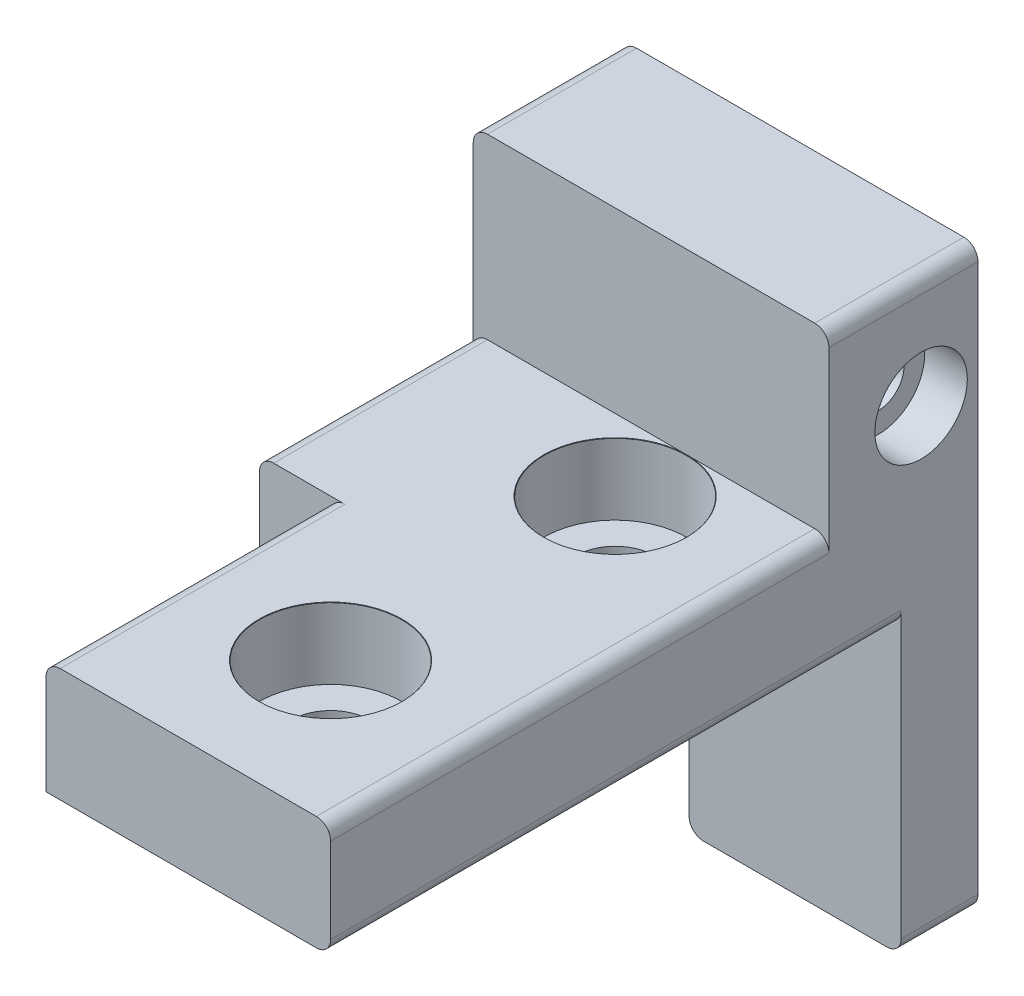
SolidWorks part; units mm, degrees
ref_plane "Front Plane" through (0, 0, 0) normal (0, 0, 1) x (1, 0, 0)
ref_plane "Top Plane" through (0, 0, 0) normal (0, 1, 0) x (1, 0, 0)
ref_plane "Right Plane" through (0, 0, 0) normal (1, 0, 0) x (0, 0, -1)
sketch "Sketch1" plane through (0, 0, 0) normal (0, 1, 0) x (1, 0, 0)
  line L0 (-10, 0) -> (-15, 0)
  line L1 (-10, -20) -> (10, -20)
  line L2 (-10, -20) -> (-10, 0)
  line L3 (-10, 20) -> (10, 20)
  line L4 (10, -20) -> (10, 20)
  line L5 (-10, -20) -> (10, 20) construction
  line L6 (-10, 20) -> (10, -20) construction
  line L7 (-15, 0) -> (-15, 20)
  line L8 (-15, 20) -> (-10, 20)
  point P0 (0, 0)
  dimension "D1" = 20
  dimension "D2" = 40
  dimension "D3" = 20
  dimension "D4" = 5
extrude "Boss-Extrude1" add sketch "Sketch1" along normal blind 8
sketch "Sketch2" plane through (0, 8, 0) normal (0, 1, 0) x (1, 0, 0)
  line L0 (0, -20) -> (0, 20) construction
  line L1 (-10, -20) -> (10, -20) construction
  line L2 (10, 20) -> (-15, 20) construction
  line L3 (-15, 10) -> (10, 10) construction
  line L4 (-15, 20) -> (-15, 0) construction
  line L5 (10, -20) -> (10, 20) construction
  point P14 (0, 10)
  point P15 (0, -10)
  dimension "D2" = 20
hole_wizard "CBORE for M5 SHCS1" positions "Sketch3" profile "Sketch4" counterbore size "M5" standard "ANSI Metric" end condition through all
sketch "Sketch3" plane through (0, 8, 0) normal (0, 1, 0) x (1, 0, 0)
  point P3 (0, 10)
  point P6 (0, -10)
sketch "Sketch4" plane through (0, 8, -10) normal (1, 0, 0) x (0, 0, 1)
  line L0 (0, 0) -> (0, 8)
  line L1 (0, 8) -> (2.75, 8)
  line L3 (2.75, 8) -> (2.75, 5)
  line L4 (5, 5) -> (2.75, 5)
  line L5 (5, 5) -> (5, 0.025)
  line L6 (5, 0.025) -> (5.025, 0)
  line L7 (5.025, 0) -> (0, 0)
  line L8 (-5, 0.025) -> (-5.025, 0) construction
  line L11 (0, -6.35) -> (0, 107.95) construction
  dimension "Thru Hole Dia." = 5.5
  dimension "Thru Hole Depth" = 8
  dimension "C'Bore Dia." = 10
  dimension "C'Bore Depth" = 5
  dimension "Near C'Sink Dia." = 10.05
  dimension "Near C'Sink Angle" = 90
sketch "Sketch5" plane through (0, 8, 0) normal (0, 1, 0) x (1, 0, 0)
  line L0 (10, -20) -> (10, 20) construction
  line L1 (-15, 18) -> (10, 18)
  line L2 (-15, 18) -> (-15, 15.025)
  line L3 (-15, 15.025) -> (10, 15.025)
  line L4 (10, 18) -> (10, 15.025)
  line L5 (10, 20) -> (-15, 20) construction
  line L6 (-15, 20) -> (-15, 0) construction
  circle A0 centre (0, 10) radius 5.025 construction
  dimension "D1" = 2
extrude "Boss-Extrude2" add sketch "Sketch5" along normal blind 12.51
sketch "Sketch6" plane through (0, 0, -18) normal (0, 0, -1) x (-1, 0, 0)
  line L0 (15, 20.51) -> (15, 8) construction
  line L1 (-10, 20.51) -> (15, 20.51)
  line L2 (-10, 20.51) -> (-10, 20)
  line L3 (-5, 17.51) -> (15, 17.51)
  line L4 (15, 20.51) -> (15, 17.51)
  line L5 (-5, 17.51) -> (-5, 8)
  line L6 (15, 8) -> (-10, 8) construction
  line L7 (-5, 8) -> (-10, 8)
  line L8 (-10, 8) -> (-10, 20)
  line L9 (15, 16.01) -> (12, 16.01)
  line L10 (12, 16.01) -> (12, 8)
  line L11 (-10, 8) -> (15, 8) construction
  line L12 (12, 8) -> (15, 8)
  line L13 (15, 8) -> (15, 16.01)
  dimension "D1" = 3
  dimension "D2" = 3
  dimension "D3" = 1.5
  dimension "D4" = 5
extrude "Boss-Extrude3" add sketch "Sketch6" along normal blind 7.5
sketch "Sketch7" plane through (0, 0, -20) normal (0, 0, -1) x (-1, 0, 0)
  line L6 (-10, 0) -> (15, 0)
  line L7 (15, 0) -> (15, 8)
  line L8 (15, 8) -> (12, 8)
  line L9 (12, 8) -> (-5, 8)
  line L10 (-5, 8) -> (-10, 8)
  line L11 (-10, 8) -> (-10, 0)
  line L12 (-10, 0) -> (15, 0)
  line L13 (15, 0) -> (15, 8)
  line L14 (15, 8) -> (12, 8)
  line L15 (12, 8) -> (-5, 8)
  line L16 (-5, 8) -> (-10, 8)
  line L17 (-10, 8) -> (-10, 0)
  dimension "D1" = 0
extrude "Boss-Extrude4" add sketch "Sketch7" along normal up to surface (5.5 mm away) up to face at (0, 15.34, -25.5)
sketch "Sketch8" plane through (0, 0, -18) normal (0, 0, -1) x (-1, 0, 0)
  line L0 (12, 16.01) -> (12, 8) construction
  line L1 (-5, 8) -> (12, 8)
  line L2 (-5, 8) -> (-5, 9.25)
  line L3 (-5, 9.25) -> (12, 9.25)
  line L4 (12, 8) -> (12, 9.25)
  dimension "D1" = 1.25
extrude "Boss-Extrude5" add sketch "Sketch8" along normal up to surface (7.5 mm away) up to face at (-5.4, 12.406, -25.5)
sketch "Sketch9" plane through (0, 0, -25.5) normal (0, 0, -1) x (-1, 0, 0)
  line L0 (-10, 0) -> (15, 0)
  line L1 (15, 0) -> (15, -5.4)
  line L2 (15, -5.4) -> (4.9, -5.4)
  line L3 (4.9, -5.4) -> (4.9, -20)
  line L4 (4.9, -20) -> (-10, -20)
  line L5 (-10, -20) -> (-10, 0)
  dimension "D1" = 5.4
  dimension "D2" = 10.1
  dimension "D3" = 20
extrude "Boss-Extrude6" add sketch "Sketch9" against normal blind 5.4
fillet "Fillet2" radius 1 10 edges at (-15, 0, -10.05) (10, 0, -0.05) (-10, 8, 10) (-15, 8, -7.5125) (10, 8, 2.4875) (-15, 20.51, -20.2625) (10, 20.51, -20.2625) (-15, -5.4, -22.8) (-4.9, -20, -22.8) (10, -20, -22.8)
sketch "Sketch10" plane through (10, 0, 0) normal (1, 0, 0) x (0, 0, -1)
  circle A0 centre (21.5, 12.75) radius 2.35 construction
  circle A1 centre (21.5, 12.75) radius 2.35
hole_wizard "CBORE for M3 SHCS1" positions "Sketch11" profile "Sketch12" counterbore size "M3" standard "ANSI Metric" end condition up to next
sketch "Sketch11" plane through (10, 0, 0) normal (1, 0, 0) x (0, 0, -1)
  point P0 (21.5, 12.75)
sketch "Sketch12" plane through (10, 12.75, -21.5) normal (0, 1, 0) x (0, 0, -1)
  line L0 (0, 0) -> (0, 5)
  line L1 (0, 5) -> (1.8, 5)
  line L3 (1.8, 5) -> (1.8, 3)
  line L4 (1.8, 3) -> (3.25, 3)
  line L5 (3.25, 3) -> (3.25, 0)
  line L7 (3.25, 0) -> (0, 0)
  line L11 (0, -6.35) -> (0, 107.95) construction
  dimension "Thru Hole Dia." = 3.6
  dimension "Thru Hole Depth" = 5
  dimension "C'Bore Dia." = 6.5
  dimension "C'Bore Depth" = 3
sketch "Sketch13" plane through (0, 0, -25.5) normal (0, 0, -1) x (-1, 0, 0)
  line L0 (-10, 7) -> (-10, 1) construction
  line L1 (-10, 7) -> (-10, 1) construction
  line L2 (-10, 4) -> (15, 4) construction
  line L3 (15, -4.4) -> (15, 16.01) construction
  line L4 (2.5, 20.51) -> (2.5, -20) construction
  line L5 (14, 20.51) -> (-9, 20.51) construction
  line L6 (-9, -20) -> (3.9, -20) construction
  circle A0 centre (10, 4) radius 2.4
  circle A1 centre (-5, 4) radius 2.4
  point P6 (10, 4)
  point P7 (-5, 4)
  point P14 (2.5, 4)
  dimension "D3" = 4.8
  dimension "D1" = 15
  dimension "D2" = 7.5
extrude "Cut-Extrude1" cut sketch "Sketch13" against normal blind 3.8
